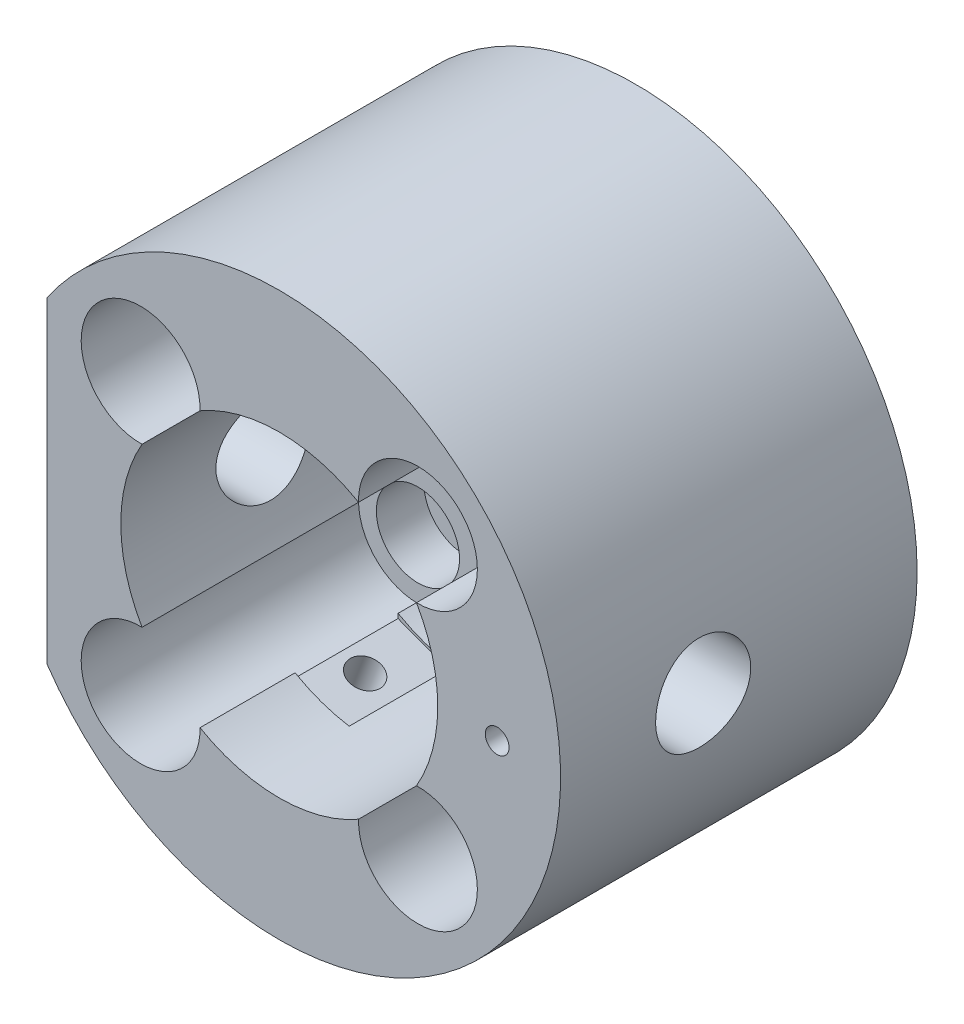
SolidWorks part; units mm, degrees
ref_plane "Alzado" through (0, 0, 0) normal (0, 0, 1) x (1, 0, 0)
ref_plane "Planta" through (0, 0, 0) normal (0, 1, 0) x (1, 0, 0)
ref_plane "Vista lateral" through (0, 0, 0) normal (1, 0, 0) x (0, 0, -1)
sketch "Croquis1" plane through (0, 0, 0) normal (0, 0, 1) x (1, 0, 0)
  line L0 (0, 0) -> (61.4595, 0) construction
  line L1 (0, 29.73) -> (43.6325, 29.73) construction
  line L2 (0, -29.73) -> (43.6325, -29.73) construction
  line L3 (0, 31.5) -> (43.6325, 31.5) construction
  circle A5 centre (0, 0) radius 35.5
  circle A6 centre (0, 0) radius 3.25
  circle A7 centre (0, 0) radius 31.5 construction
  circle A8 centre (0, 24.75) radius 4.98 construction
  circle A9 centre (0, -24.75) radius 4.98 construction
  circle A10 centre (0, 0) radius 24.75 construction
  circle A11 centre (0, 24.75) radius 3.15 construction
  circle A12 centre (0, 0) radius 24.75 construction
  circle A13 centre (17.5009, 17.5009) radius 3.15
  circle A14 centre (0, 0) radius 24.75 construction
  circle A15 centre (24.75, 0) radius 3.15 construction
  circle A16 centre (0, 0) radius 24.75 construction
  circle A17 centre (17.5009, -17.5009) radius 3.15
  circle A18 centre (0, 0) radius 24.75 construction
  circle A19 centre (0, -24.75) radius 3.15 construction
  circle A20 centre (0, 0) radius 24.75 construction
  circle A21 centre (-17.5009, -17.5009) radius 3.15
  circle A22 centre (0, 0) radius 24.75 construction
  circle A23 centre (-24.75, 0) radius 3.15 construction
  circle A24 centre (0, 0) radius 24.75 construction
  circle A25 centre (-17.5009, 17.5009) radius 3.15
  point P16 (0, 0)
  point P41 (0, 0)
  dimension "D1" = 9.96
  dimension "D3" = 63
  dimension "D6" = 71
  dimension "D7" = 6.5
  dimension "D4" = 6.3
  dimension "D2" = 1.77
  dimension "D5" = 8
extrude "Saliente-Extruir1" add sketch "Croquis1" along normal blind 5
sketch "Croquis2" plane through (0, 0, 5) normal (0, 0, 1) x (1, 0, 0)
  line L0 (-29.33, 20) -> (-29.33, -20)
  arc A0 (-29.33, -20) -> (-29.33, 20) centre (0, 0) ccw
  circle A3 centre (17.5009, 17.5009) radius 7.5
  circle A9 centre (-17.5009, 17.5009) radius 7.5
  arc A13 (-29.33, -20) -> (-29.33, 20) centre (0, 0) ccw
  circle A14 centre (0, 0) radius 20
  circle A15 centre (-17.5009, 17.5009) radius 3.15 construction
  circle A16 centre (0, 0) radius 24.75 construction
  circle A18 centre (0, 0) radius 24.75 construction
  circle A19 centre (17.5009, -17.5009) radius 7.5
  circle A20 centre (0, 0) radius 24.75 construction
  circle A21 centre (-17.5009, -17.5009) radius 7.5
  circle A22 centre (0, 0) radius 24.75 construction
  point P21 (0, 0)
  circle M3 centre (0, 0) radius 35.5
  dimension "D1" = 71
  dimension "D4" = 40
  dimension "D3" = 15
  dimension "D2" = 40
  dimension "D6" = 4
extrude "Saliente-Extruir2" add sketch "Croquis2" along normal blind 35 contours L0 A21 A14 A9 A3 A19 M3 region at (10.1816, 33.0037, 5)
sketch "Croquis3" plane through (-29.33, 0, 0) normal (-1, 0, 0) x (0, 0, 1)
  circle A0 centre (22, 0) radius 6
  dimension "D1" = 12
  dimension "D2" = 22
extrude "Cortar-Extruir1" cut sketch "Croquis3" against normal through all
sketch "Croquis4" plane through (0, 0, 40) normal (0, 0, 1) x (1, 0, 0)
  circle A0 centre (27.5, 0) radius 1.5
  circle A1 centre (0, 0) radius 27.5 construction
  dimension "D1" = 55
  dimension "D2" = 3
extrude "Cortar-Extruir2" cut sketch "Croquis4" against normal up to next
sketch "Croquis5" plane through (0, 0, 5) normal (0, 0, 1) x (1, 0, 0)
  line L0 (-16.2021, -31.5871) -> (-8.7178, -34.4129)
  line L1 (-12.4599, -33) -> (0, 0) construction
  line L2 (-10.9036, -17.554) -> (-3.4193, -20.3799) construction
  arc A0 (-29.33, -20) -> (-29.33, 20) centre (0, 0) ccw construction
  point P10 (-7.1614, -18.967)
  dimension "D1" = 8
  dimension "D2" = 33
  dimension "D3" = 8
  dimension "D4" = 15
extrude "Cortar-Extruir-Lámina1" cut sketch "Croquis5" along normal offset from surface (13 mm away) 11 from offset 11 thin up to face at (29, 0, 40) thin type one direction wall 2
sketch "Croquis6" plane through (-12.4599, -33, 0) normal (-0.3532, -0.9355, 0) x (0.9355, -0.3532, 0)
  line L0 (-4, 29) -> (4, 29) construction
  line L2 (-4, 29) -> (-4, 16) construction
  circle A0 centre (0, 22) radius 2
  dimension "D1" = 4
  dimension "D2" = 7
  dimension "D3" = 4
extrude "Cortar-Extruir3" cut sketch "Croquis6" against normal up to next
sketch "Croquis7" plane through (0, 0, 5) normal (0, 0, 1) x (1, 0, 0)
  line L0 (-10.9036, -17.554) -> (-3.4193, -20.3799)
extrude "Cortar-Extruir-Lámina2" cut sketch "Croquis7" along normal blind 13 from offset 10 thin thin type one direction reverse wall 2
sketch "Croquis10" plane through (0, 0, 0) normal (0, 0, -1) x (-1, 0, 0)
  circle A1 centre (0, 0) radius 3.25
  circle A2 centre (0, 0) radius 3.25
  circle A3 centre (-17.5009, 17.5009) radius 3.15
  circle A4 centre (-17.5009, 17.5009) radius 3.15
  circle A5 centre (-17.5009, -17.5009) radius 3.15
  circle A6 centre (-17.5009, -17.5009) radius 3.15
  circle A7 centre (17.5009, -17.5009) radius 3.15
  circle A8 centre (17.5009, -17.5009) radius 3.15
  circle A9 centre (17.5009, 17.5009) radius 3.15
  circle A10 centre (17.5009, 17.5009) radius 3.15
  circle M6 centre (0, 0) radius 35.5
  circle M7 centre (0, 0) radius 3.25
  circle M8 centre (-17.5009, 17.5009) radius 3.15
  circle M9 centre (-17.5009, -17.5009) radius 3.15
  circle M10 centre (17.5009, -17.5009) radius 3.15
  circle M11 centre (17.5009, 17.5009) radius 3.15
  dimension "D1" = 0
  dimension "D2" = 0
  dimension "D3" = 0
  dimension "D4" = 0
  dimension "D5" = 0
extrude "Saliente-Extruir4" add sketch "Croquis10" along normal blind 5 contours M6 M7 M9 M11 M10 M8 region at (34.4959, 0, 0)
sketch "Croquis8" plane through (0, 0, 5) normal (0, 0, 1) x (1, 0, 0)
  circle A0 centre (-17.5009, -17.5009) radius 5.25
  circle A1 centre (0, 0) radius 20 construction
  circle A2 centre (0, 0) radius 24.75 construction
  arc A3 (-17.3187, 10.0031) -> (-17.3187, -10.0031) centre (0, 0) ccw construction
  circle A4 centre (-17.5009, 17.5009) radius 5.25
  circle A5 centre (0, 0) radius 24.75 construction
  circle A6 centre (17.5009, 17.5009) radius 5.25
  circle A7 centre (0, 0) radius 24.75 construction
  circle A8 centre (17.5009, -17.5009) radius 5.25
  circle A9 centre (0, 0) radius 24.75 construction
  point P23 (0, 0)
  dimension "D1" = 10.5
  dimension "D2" = 4
extrude "Cortar-Extruir4" cut sketch "Croquis8" against normal blind 6
